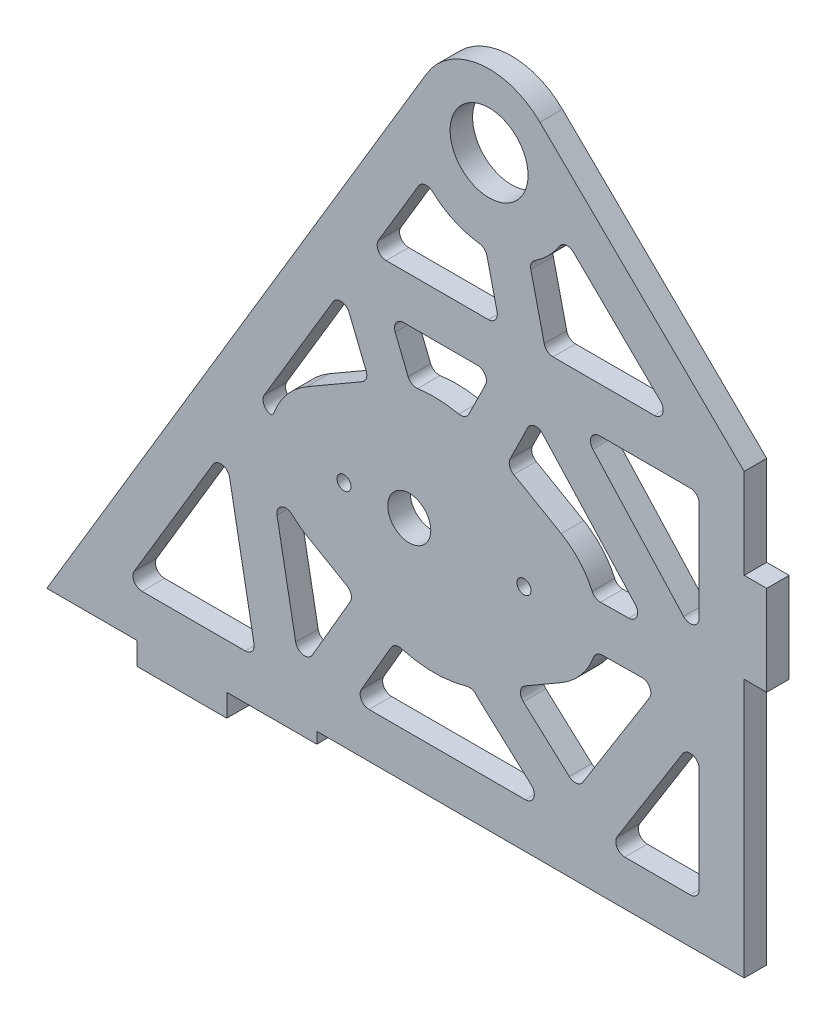
SolidWorks part; units mm, degrees
ref_plane "Front Plane" through (0, 0, 0) normal (0, 0, 1) x (1, 0, 0)
ref_plane "Top Plane" through (0, 0, 0) normal (0, 1, 0) x (1, 0, 0)
ref_plane "Right Plane" through (0, 0, 0) normal (1, 0, 0) x (0, 0, -1)
sketch "Sketch2" plane through (0, 0, 0) normal (0, 0, 1) x (1, 0, 0)
  line L1 (50.8, 6.35) -> (76.2, 6.35)
  line L2 (0, 6.35) -> (107.2144, 185.7594)
  line L4 (76.2, 6.35) -> (76.2, 9.525)
  line L6 (0, 6.35) -> (0, 0)
  line L7 (0, 0) -> (25.4, 0) construction
  line L8 (25.4, 6.35) -> (25.4, 0)
  line L13 (76.2, 9.525) -> (83.9864, 9.525)
  line L17 (0, -29.7981) -> (203.2, -29.7981) construction
  line L20 (196.85, 9.525) -> (196.85, 82.55)
  line L22 (196.85, 133.35) -> (139.2046, 189.8844)
  line L23 (196.85, 107.95) -> (196.85, 133.35)
  line L24 (196.85, 107.95) -> (203.2, 107.95)
  line L26 (196.85, 82.55) -> (203.2, 82.55)
  line L27 (203.2, 107.95) -> (203.2, 82.55)
  line L28 (83.9864, 9.525) -> (196.85, 9.525)
  line L29 (0, 6.35) -> (25.4, 6.35)
  line L30 (25.4, 0) -> (50.8, 0)
  line L31 (50.8, 0) -> (50.8, 6.35)
  arc A0 (139.2046, 189.8844) -> (107.2144, 185.7594) centre (124.8331, 175.2305) ccw
  circle A1 centre (124.8331, 175.2305) radius 11 construction
  circle A2 centre (124.8331, 175.2305) radius 4 construction
  circle A3 centre (124.8331, 175.2305) radius 11
  dimension "D3" = 22
  dimension "D4" = 9.525
  dimension "D5" = 8
  dimension "D6" = 22
  dimension "D1" = 168.8805
  dimension "D2" = 124.8331
  dimension "D7" = 6.35
  dimension "D8" = 25.4
  dimension "D9" = 3.175
  dimension "D10" = 6.35
  dimension "D11" = 73.025
  dimension "D12" = 203.2
  dimension "D13" = 76.2
  dimension "D14" = 6.35
  dimension "D15" = 25.4
  dimension "D16" = 6.35
  dimension "D17" = 25.4
  dimension "D18" = 25.4
extrude "Boss-Extrude1" add sketch "Sketch2" along normal blind 6.35 contours L22 A0 L2 L29 L8 L30 L31 L1 L4 L13 L28 L20 L26 L27 L24 L23 A3 region at (118.2801, 80.4306, 0)
sketch "Sketch4" [suppressed] plane through (0, 0, 6.35) normal (0, 0, 1) x (1, 0, 0)
  line L0 (1673.3123, 156.2334) -> (1577.5737, -3.9728)
  line L1 (1691.5051, 171.4226) -> (1750.822, 113.2489)
  line L2 (1684.7881, 175.4367) -> (1577.5737, -3.9728) construction
  line L3 (1590.9538, 18.4171) -> (1750.822, 18.4171)
  line L4 (1686.3016, 73.3904) -> (1617.2071, 143.6449) construction
  line L7 (1681.7742, 68.9378) -> (1612.6797, 139.1923)
  line L10 (1690.8289, 77.843) -> (1621.7344, 148.0975)
  line L13 (1566.672, 2.5421) -> (1566.672, -3.8079)
  line L14 (1566.672, -3.8079) -> (1592.072, -3.8079)
  line L15 (1592.072, -3.8079) -> (1592.072, 2.5421)
  line L16 (1592.072, 2.5421) -> (1642.872, 2.5421)
  line L17 (1642.872, 2.5421) -> (1642.872, 5.7171)
  line L18 (1642.872, 5.7171) -> (1763.522, 5.7171)
  line L24 (1763.522, 5.7171) -> (1763.522, 78.7421)
  line L25 (1673.8864, 181.9515) -> (1566.672, 2.5421)
  line L26 (1566.672, 2.5421) -> (1566.672, -3.8079)
  line L27 (1566.672, -3.8079) -> (1592.072, -3.8079)
  line L28 (1592.072, -3.8079) -> (1592.072, 2.5421)
  line L29 (1592.072, 2.5421) -> (1642.872, 2.5421)
  line L30 (1642.872, 2.5421) -> (1642.872, 5.7171)
  line L31 (1642.872, 5.7171) -> (1763.522, 5.7171)
  line L38 (1673.8864, 181.9515) -> (1566.672, 2.5421)
  line L39 (1686.3016, 73.3904) -> (1776.688, 147.3217) construction
  line L42 (1682.2812, 78.3056) -> (1772.6676, 152.2368)
  line L45 (1690.3219, 68.4752) -> (1780.7084, 142.4065)
  line L46 (1686.3016, 73.3904) -> (1535.3984, -21.6576) construction
  line L47 (1750.822, 113.2489) -> (1750.822, 18.4171)
  line L48 (1689.6858, 68.0174) -> (1538.7827, -27.0307)
  line L49 (1682.9173, 78.7634) -> (1532.0142, -16.2846)
  line L50 (1686.3016, 73.3904) -> (1767.8024, 12.8123) construction
  line L51 (1690.0896, 78.4868) -> (1771.5905, 17.9087)
  line L52 (1682.5135, 68.294) -> (1764.0144, 7.7159)
  line L53 (1691.5051, 171.4226) -> (1681.8948, -9.6316) construction
  line L54 (1697.8462, 171.086) -> (1688.2358, -9.9682)
  line L55 (1685.1641, 171.7592) -> (1675.5537, -9.2951)
  line L60 (1763.522, 5.7171) -> (1763.522, 78.7421)
  line L61 (1763.522, 129.5421) -> (1705.8766, 186.0765)
  line L62 (1763.522, 129.5421) -> (1705.8766, 186.0765)
  line L68 (1763.522, 78.7421) -> (1769.872, 78.7421)
  line L69 (1763.522, 78.7421) -> (1769.872, 78.7421)
  line L70 (1769.872, 78.7421) -> (1769.872, 104.1421)
  line L71 (1769.872, 78.7421) -> (1769.872, 104.1421)
  line L72 (1769.872, 104.1421) -> (1763.522, 104.1421)
  line L73 (1769.872, 104.1421) -> (1763.522, 104.1421)
  line L74 (1763.522, 104.1421) -> (1763.522, 129.5421)
  line L75 (1763.522, 104.1421) -> (1763.522, 129.5421)
  arc A1 (1705.8766, 186.0765) -> (1673.8864, 181.9515) centre (1691.5051, 171.4226) ccw
  arc A2 (1705.8766, 186.0765) -> (1673.8864, 181.9515) centre (1691.5051, 171.4226) ccw
  circle A4 centre (1691.5051, 171.4226) radius 23.7
  circle A5 centre (1691.5051, 171.4226) radius 23.7
  arc A14 (1681.7742, 68.9378) -> (1690.8289, 77.843) centre (1686.3016, 73.3904) ccw
  arc A15 (1621.7344, 148.0975) -> (1612.6797, 139.1923) centre (1617.2071, 143.6449) ccw
  arc A16 (1682.2812, 78.3056) -> (1690.3219, 68.4752) centre (1686.3016, 73.3904) ccw
  arc A17 (1780.7084, 142.4065) -> (1772.6676, 152.2368) centre (1776.688, 147.3217) ccw
  arc A18 (1689.6858, 68.0174) -> (1682.9173, 78.7634) centre (1686.3016, 73.3904) ccw
  arc A19 (1532.0142, -16.2846) -> (1538.7827, -27.0307) centre (1535.3984, -21.6576) ccw
  arc A20 (1690.0896, 78.4868) -> (1682.5135, 68.294) centre (1686.3016, 73.3904) ccw
  arc A21 (1764.0144, 7.7159) -> (1771.5905, 17.9087) centre (1767.8024, 12.8123) ccw
  arc A22 (1697.8462, 171.086) -> (1685.1641, 171.7592) centre (1691.5051, 171.4226) ccw
  arc A23 (1675.5537, -9.2951) -> (1688.2358, -9.9682) centre (1681.8948, -9.6316) ccw
  point P15 (1651.7543, 108.5176)
  point P28 (1731.4948, 110.356)
  point P35 (1610.85, 25.8664)
  point P42 (1727.052, 43.1013)
  point P50 (1686.6999, 80.8955)
  dimension "D6" = 6.35
  dimension "D4" = 12.7
  dimension "D5" = 12.7
  dimension "D1" = 0
  dimension "D2" = 12.7
  dimension "D3" = 12.7
extrude "Cut-Extrude1" [suppressed] cut sketch "Sketch4" against normal through all contours L49 L7 L0 | A5 L0 L10 L55 | A5 L54 L42 L1 | L45 L51 L47 L1 | L52 L54 L3 | L55 L48 L3
fillet "Fillet1" [suppressed] radius 2.54
sketch "Sketch5" plane through (0, 0, 6.35) normal (0, 0, 1) x (1, 0, 0)
  arc A0 (107.7056, 77.303) -> (97.4063, 78.1479) centre (102.3066, 74.6857) ccw construction
  arc A1 (107.7056, 77.303) -> (97.4063, 78.1479) centre (102.3066, 74.6857) ccw construction
  arc A2 (107.7056, 77.303) -> (97.4063, 78.1479) centre (102.3066, 74.6857) cw construction
  arc A3 (107.7742, 77.3363) -> (97.344, 78.1919) centre (102.3066, 74.6857) cw
  arc A4 (107.7742, 77.3363) -> (97.344, 78.1919) centre (102.3066, 74.6857) ccw
  dimension "D1" = 0.0762
extrude "Cut-Extrude2" cut sketch "Sketch5" against normal through all both and the other way through all
sketch "Sketch6" plane through (0, 0, 0) normal (0, 0, -1) x (-1, 0, 0)
  circle A0 centre (-83.8831, 74.1134) radius 1.9844 construction
  circle A1 centre (-134.6831, 74.1134) radius 1.9844 construction
  circle A2 centre (-83.8831, 74.1134) radius 1.9844
  circle A3 centre (-134.6831, 74.1134) radius 1.9844
extrude "Cut-Extrude3" cut sketch "Sketch6" against normal through all both and the other way through all
sketch "Sketch7" plane through (0, 0, 0) normal (0, 0, -1) x (-1, 0, 0)
  line L0 (-184.15, 128.017) -> (-87.5027, 128.017) construction
  line L1 (-184.15, 134.367) -> (-87.5027, 134.367)
  line L2 (-184.15, 121.667) -> (-87.5027, 121.667)
  line L3 (-124.8331, 175.2305) -> (-135.8263, 128.017) construction
  line L4 (-138.8522, 66.8967) -> (-119.8078, 55.8949) construction
  line L5 (-119.8078, 92.3319) -> (-138.8522, 81.3301) construction
  line L6 (-79.7141, 81.3301) -> (-98.7585, 92.3319) construction
  line L7 (-98.7585, 55.8949) -> (-79.7141, 66.8967) construction
  line L8 (-145.205, 55.8998) -> (-126.1606, 44.898)
  line L9 (-92.4057, 44.898) -> (-73.3613, 55.8998)
  line L10 (-73.3613, 92.327) -> (-92.4057, 103.3288)
  line L11 (-126.1606, 103.3288) -> (-145.205, 92.327)
  line L12 (-118.6486, 173.7905) -> (-129.6418, 126.5769)
  line L13 (-131.0177, 176.6706) -> (-142.0109, 129.457)
  line L14 (-135.8263, 128.017) -> (-109.2831, 74.1134) construction
  line L15 (-130.1296, 130.8222) -> (-103.5864, 76.9186)
  line L16 (-141.5231, 125.2117) -> (-114.9799, 71.3082)
  line L17 (-109.2831, 74.1134) -> (-87.5027, 128.017) construction
  line L18 (-115.1707, 76.4923) -> (-93.3902, 130.3959)
  line L19 (-103.3956, 71.7344) -> (-81.6151, 125.638)
  line L20 (-109.2831, 74.1134) -> (-184.15, 75.121) construction
  line L21 (-109.3686, 67.764) -> (-184.2355, 68.7716)
  line L22 (-109.1977, 80.4628) -> (-184.0645, 81.4704)
  line L23 (-135.8263, 128.017) -> (-184.15, 75.121) construction
  line L24 (-131.1382, 123.734) -> (-179.4618, 70.838)
  line L25 (-140.5145, 132.2999) -> (-188.8382, 79.4039)
  line L26 (-109.2831, 74.1134) -> (-55.2901, 74.1134) construction
  line L27 (-109.2831, 80.4634) -> (-55.2901, 80.4634)
  line L28 (-109.2831, 67.7634) -> (-55.2901, 67.7634)
  line L29 (-184.15, 75.121) -> (-151.0555, 22.225) construction
  line L30 (-178.7668, 78.489) -> (-145.6723, 25.593)
  line L31 (-189.5332, 71.753) -> (-156.4387, 18.857)
  line L32 (-151.0555, 22.225) -> (-126.1606, 44.898) construction
  line L33 (-155.3312, 26.9197) -> (-130.4364, 49.5927)
  line L34 (-146.7797, 17.5303) -> (-121.8849, 40.2033)
  line L35 (-92.4057, 44.898) -> (-68.3801, 3.5805) construction
  line L36 (-130.3121, 180.8172) -> (-184.15, 128.017)
  line L37 (-184.15, 128.017) -> (-184.15, 22.225)
  line L38 (-184.15, 22.225) -> (-63.5, 22.225)
  line L39 (-63.5, 22.225) -> (-63.5, 19.05)
  line L40 (-63.5, 19.05) -> (-22.3844, 19.05)
  line L41 (-22.3844, 19.05) -> (-118.1161, 179.2446)
  line L42 (-130.3121, 180.8172) -> (-184.15, 128.017)
  line L43 (-184.15, 128.017) -> (-184.15, 22.225)
  line L44 (-184.15, 22.225) -> (-63.5, 22.225)
  line L45 (-63.5, 22.225) -> (-63.5, 19.05)
  line L46 (-63.5, 19.05) -> (-22.3844, 19.05)
  line L47 (-22.3844, 19.05) -> (-118.1161, 179.2446)
  line L48 (-86.9163, 48.09) -> (-62.8907, 6.7726)
  line L49 (-97.8951, 41.706) -> (-73.8694, 0.3885)
  line L50 (-68.3801, 3.5805) -> (-55.2901, 74.1134) construction
  line L51 (-74.6234, 4.7392) -> (-61.5335, 75.2721)
  line L52 (-62.1367, 2.4219) -> (-49.0467, 72.9547)
  circle A0 centre (-124.8331, 175.2305) radius 11
  circle A1 centre (-124.8331, 175.2305) radius 23.7
  arc A2 (-118.1161, 179.2446) -> (-130.3121, 180.8172) centre (-124.8331, 175.2305) ccw
  arc A3 (-118.1161, 179.2446) -> (-130.3121, 180.8172) centre (-124.8331, 175.2305) ccw
  arc A4 (-138.8522, 81.3301) -> (-138.8522, 66.8967) centre (-134.6831, 74.1134) ccw construction
  arc A6 (-79.7141, 66.8967) -> (-79.7141, 81.3301) centre (-83.8831, 74.1134) ccw construction
  arc A8 (-119.8078, 92.3319) -> (-98.7585, 92.3319) centre (-109.2831, 74.1134) cw construction
  arc A9 (-119.8078, 55.8949) -> (-98.7585, 55.8949) centre (-109.2831, 74.1134) ccw construction
  arc A10 (-126.1606, 44.898) -> (-92.4057, 44.898) centre (-109.2831, 74.1134) ccw
  arc A11 (-73.3613, 55.8998) -> (-73.3613, 92.327) centre (-83.8831, 74.1134) ccw
  arc A12 (-126.1606, 103.3288) -> (-92.4057, 103.3288) centre (-109.2831, 74.1134) cw
  arc A13 (-145.205, 92.327) -> (-145.205, 55.8998) centre (-134.6831, 74.1134) ccw
  arc A14 (-184.15, 134.367) -> (-184.15, 121.667) centre (-184.15, 128.017) ccw
  arc A15 (-87.5027, 121.667) -> (-87.5027, 134.367) centre (-87.5027, 128.017) ccw
  arc A16 (-118.6486, 173.7905) -> (-131.0177, 176.6706) centre (-124.8331, 175.2305) ccw
  arc A17 (-142.0109, 129.457) -> (-129.6418, 126.5769) centre (-135.8263, 128.017) ccw
  arc A18 (-130.1296, 130.8222) -> (-141.5231, 125.2117) centre (-135.8263, 128.017) ccw
  arc A19 (-114.9799, 71.3082) -> (-103.5864, 76.9186) centre (-109.2831, 74.1134) ccw
  arc A20 (-115.1707, 76.4923) -> (-103.3956, 71.7344) centre (-109.2831, 74.1134) ccw
  arc A21 (-81.6151, 125.638) -> (-93.3902, 130.3959) centre (-87.5027, 128.017) ccw
  arc A22 (-109.3686, 67.764) -> (-109.1977, 80.4628) centre (-109.2831, 74.1134) ccw
  arc A23 (-184.0645, 81.4704) -> (-184.2355, 68.7716) centre (-184.15, 75.121) ccw
  arc A24 (-131.1382, 123.734) -> (-140.5145, 132.2999) centre (-135.8263, 128.017) ccw
  arc A25 (-188.8382, 79.4039) -> (-179.4618, 70.838) centre (-184.15, 75.121) ccw
  arc A26 (-109.2831, 80.4634) -> (-109.2831, 67.7634) centre (-109.2831, 74.1134) ccw
  arc A27 (-55.2901, 67.7634) -> (-55.2901, 80.4634) centre (-55.2901, 74.1134) ccw
  arc A28 (-178.7668, 78.489) -> (-189.5332, 71.753) centre (-184.15, 75.121) ccw
  arc A29 (-156.4387, 18.857) -> (-145.6723, 25.593) centre (-151.0555, 22.225) ccw
  arc A30 (-155.3312, 26.9197) -> (-146.7797, 17.5303) centre (-151.0555, 22.225) ccw
  arc A31 (-121.8849, 40.2033) -> (-130.4364, 49.5927) centre (-126.1606, 44.898) ccw
  arc A32 (-86.9163, 48.09) -> (-97.8951, 41.706) centre (-92.4057, 44.898) ccw
  arc A33 (-73.8694, 0.3885) -> (-62.8907, 6.7726) centre (-68.3801, 3.5805) ccw
  arc A34 (-74.6234, 4.7392) -> (-62.1367, 2.4219) centre (-68.3801, 3.5805) ccw
  arc A35 (-49.0467, 72.9547) -> (-61.5335, 75.2721) centre (-55.2901, 74.1134) ccw
  point P28 (-135.8263, 128.017)
  point P35 (-130.3297, 151.6237)
  point P43 (-122.5547, 101.0652)
  point P52 (-98.3929, 101.0652)
  point P59 (-146.7166, 74.6172)
  point P66 (-159.9882, 101.569)
  point P75 (-82.2866, 74.1134)
  point P82 (-167.6027, 48.673)
  point P88 (-138.608, 33.5615)
  point P94 (-80.3929, 24.2393)
  point P101 (-61.8351, 38.847)
  point P106 (-62.1633, 22.225)
  point P107 (0, 0)
  point P108 (0, 0)
  point P109 (-56.8991, 22.225)
  point P110 (0, 0)
  point P111 (-68.3801, 3.5805)
  point P112 (0, 0)
  dimension "D3" = 22
  dimension "D5" = 6.35
  dimension "D1" = 12.7
  dimension "D2" = 12.7
  dimension "D4" = 12.7
extrude "Cut-Extrude4" cut sketch "Sketch7" against normal blind 50.8 contours A1 L42 L1 L13 | L2 L43 L25 | A1 L12 L1 L47 | L15 A12 L18 L2 | A13 L11 L16 L24 L22 | L43 L44 L31 | A13 L21 L30 L33 L8 | A32 A10 A31 L34 L44 L49 | A11 L9 L48 L44 L51 L28 | L52 L46 L47 | A11 L27 L47 L19 L10 region at (152.6067, 145.6167, 0) region at (172.8428, 109.2899, 0) region at (110.7733, 143.6778, 0) region at (147.643, 97.0565, 0) region at (175.6153, 35.8663, 0) region at (111.0261, 115.2595, 0) region at (152.4599, 52.1391, 0) region at (77.5425, 101.4944, 0) region at (111.9941, 30.3726, 0) region at (73.8248, 44.4255, 0) region at (43.9324, 34.6557, 0)
fillet "Fillet2" radius 2.54 14 edges at (154.5328, 81.0729, 3.175) (131.931, 48.2315, 3.175) (184.15, 121.667, 3.175) (149.7071, 32.0419, 3.175) (172.589, 68.6148, 3.175) (154.9202, 68.377, 3.175) (125.6214, 121.667, 3.175) (150.2283, 121.667, 3.175) (96.9173, 121.667, 3.175) (123.8266, 151.5519, 3.175) (146.284, 165.1532, 3.175) (118.2252, 106.6469, 3.175) (184.15, 84.5357, 3.175) (120.3877, 42.2531, 3.175)
fillet "Fillet3" radius 2.54 6 edges at (71.8761, 22.225, 3.175) (86.5671, 22.225, 3.175) (140.8677, 134.367, 3.175) (22.3844, 19.05, 3.175) (59.0507, 19.05, 3.175) (86.9072, 48.0744, 3.175)
fillet "Fillet4" radius 2.54 13 edges at (71.3783, 22.225, 3.175) (102.7563, 107.2161, 3.175) (91.2974, 134.367, 3.175) (184.15, 22.225, 3.175) (98.1786, 42.2531, 3.175) (83.4167, 121.1795, 3.175) (90.9656, 102.4969, 3.175) (177.6752, 134.367, 3.175) (59.0848, 80.4634, 3.175) (158.5459, 22.225, 3.175) (141.6249, 22.225, 3.175) (184.15, 63.1488, 3.175) (50.3621, 65.867, 3.175)
fillet "Fillet5" radius 2.54 2 edges at (63.8302, 80.4634, 3.175) (106.6403, 160.0413, 3.175)
fillet "Fillet6" radius 2.54 5 edges at (63.8302, 67.7634, 3.175) (137.4132, 116.8653, 3.175) (169.9224, 81.2801, 3.175) (129.7317, 101.2658, 3.175) (127.8279, 134.367, 3.175)
fillet "Fillet7" radius 2.54 2 edges at (62.927, 67.7634, 3.175) (136.1957, 154.4319, 3.175)
